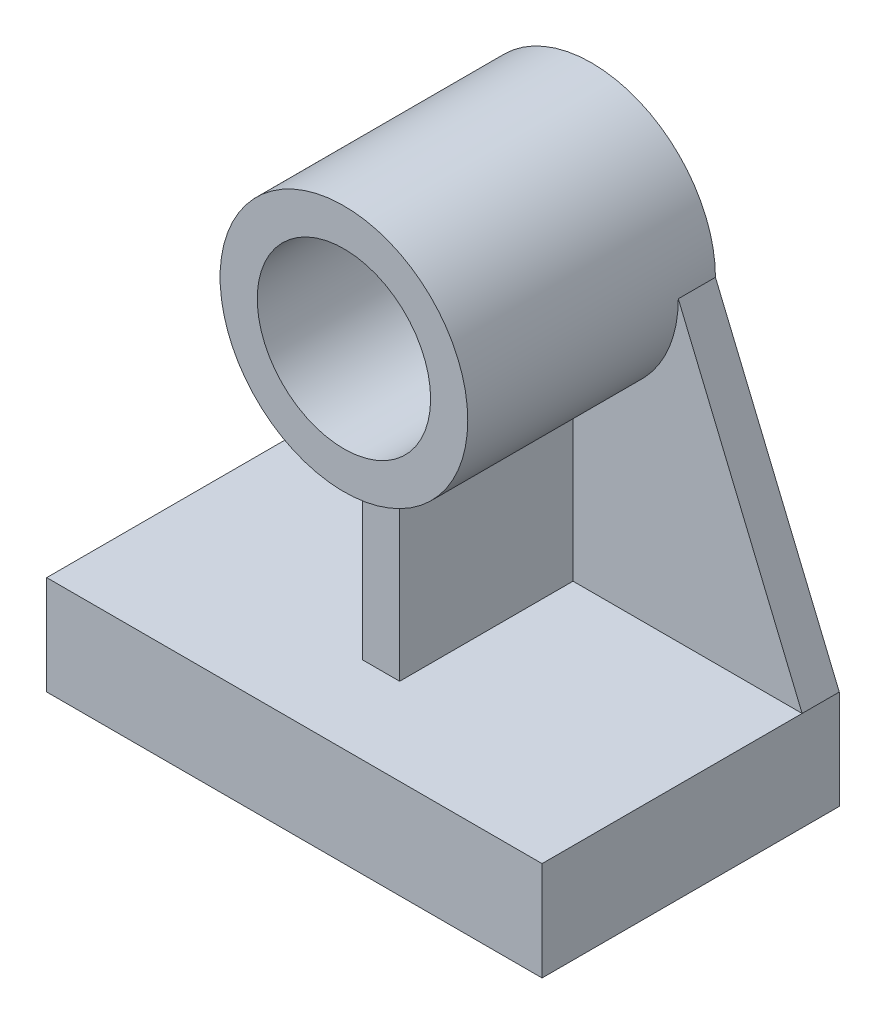
SolidWorks part; units mm, degrees
material "6063-T6"
ref_plane "Front Plane" through (0, 0, 0) normal (0, 0, 1) x (1, 0, 0)
ref_plane "Top Plane" through (0, 0, 0) normal (0, 1, 0) x (1, 0, 0)
ref_plane "Right Plane" through (0, 0, 0) normal (1, 0, 0) x (0, 0, -1)
sketch "Sketch1" plane through (0, 0, 0) normal (0, 0, 1) x (1, 0, 0)
  line L0 (-63.5, 0) -> (-127, -152.4)
  line L1 (63.5, 0) -> (127, -152.4)
  line L3 (-127, -203.2) -> (127, -203.2)
  line L4 (-127, -203.2) -> (-127, -152.4)
  line L5 (-127, -152.4) -> (127, -152.4)
  line L6 (127, -203.2) -> (127, -152.4)
  line L8 (9.525, -62.7816) -> (9.525, -152.4)
  line L9 (9.525, -152.4) -> (-9.525, -152.4)
  line L10 (-9.525, -62.7816) -> (-9.525, -152.4)
  circle A0 centre (0, 0) radius 44.45
  circle A1 centre (0, 0) radius 63.5
  point P4 (0, -203.2)
  point P5 (0, -152.4)
  point P6 (127, -203.2)
  point P7 (127, -152.4)
  point P8 (-127, -203.2)
  point P9 (-127, -152.4)
  point P10 (9.525, -152.4)
  point P11 (-9.525, -152.4)
  point P12 (9.525, 0)
  dimension "D1" = 88.9
  dimension "D2" = 127
extrude "Boss-Extrude1" add sketch "Sketch1" along normal blind 107.95 contours A1 L10 L5 L8 region at (0, -107.8303, 0)
extrude "Boss-Extrude2" add sketch "Sketch1<3>" along normal blind 19.05 contours A1 L0 L5 L10 | A1 L8 L5 L1 region at (-59.7646, -100.2014, 0) region at (59.7646, -100.2014, 0)
sketch "Sketch1<3>" plane through (0, 0, 0) normal (0, 0, 1) x (1, 0, 0) same geometry as "Sketch1"
extrude "Boss-Extrude3" add sketch "Sketch1<4>" along normal blind 127 contours A1 A0 region at (0, 61.7039, 0)
sketch "Sketch1<4>" plane through (0, 0, 0) normal (0, 0, 1) x (1, 0, 0) same geometry as "Sketch1"
extrude "Boss-Extrude4" add sketch "Sketch1<5>" along normal blind 152.4 contours L3 L6 L5 L4 region at (0, -177.8, 0)
sketch "Sketch1<5>" plane through (0, 0, 0) normal (0, 0, 1) x (1, 0, 0) same geometry as "Sketch1"
